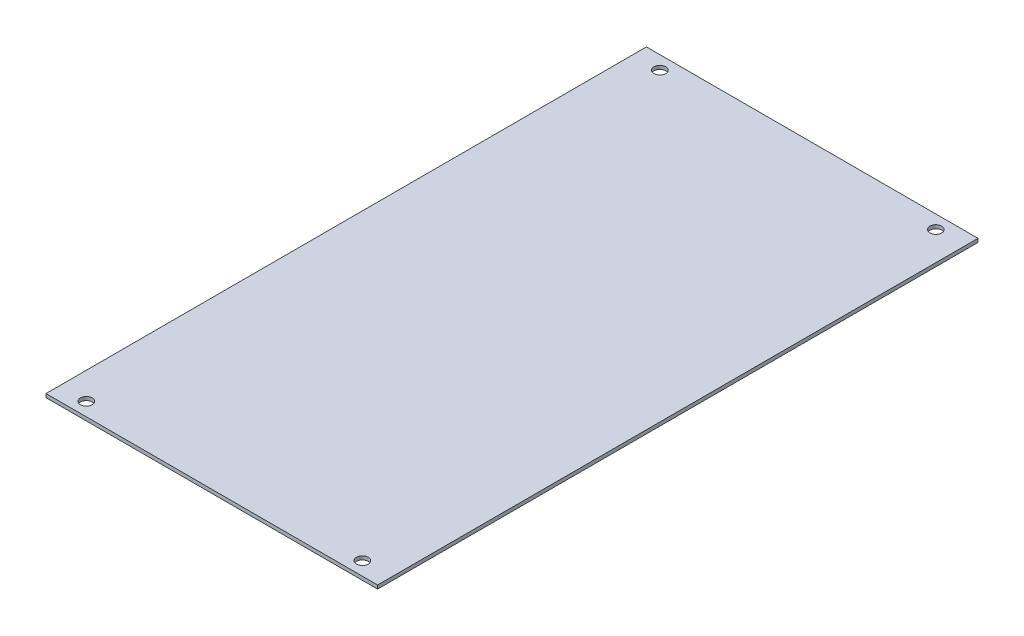
SolidWorks part; units mm, degrees
material "1.4301 (X5CrNi18-10)"
ref_plane "Vorne" through (0, 0, 0) normal (0, 0, 1) x (1, 0, 0)
ref_plane "Oben" through (0, 0, 0) normal (0, 1, 0) x (1, 0, 0)
ref_plane "Rechts" through (0, 0, 0) normal (1, 0, 0) x (0, 0, -1)
sketch "Skizze2" plane through (0, 0, 0) normal (0, 1, 0) x (1, 0, 0)
  line L1 (-92.5, 167.5) -> (92.5, 167.5)
  line L2 (-92.5, 167.5) -> (-92.5, -167.5)
  line L3 (-92.5, -167.5) -> (92.5, -167.5)
  line L4 (92.5, 167.5) -> (92.5, -167.5)
  line L5 (-92.5, 167.5) -> (92.5, -167.5) construction
  line L6 (-92.5, -167.5) -> (92.5, 167.5) construction
  point P0 (0, 0)
  dimension "D1" = 185
  dimension "D2" = 335
sheet metal parameters "Blech1" thickness 2 parameters "D1"=0.1, "Dicke"=2
base flange "Basis-Blech1" sketch "Skizze2" thickness 2 reverse thickness direction no parameters "D1"=0.1
hole_wizard "Durchgangsloch für M61" positions "Skizze27" profile "Skizze26" hole size "M6" standard "Gabler-Normteile" end condition through all
sketch "Skizze27" plane through (0, -2, 0) normal (0, -1, 0) x (-1, 0, 0)
  line L0 (0, 0) -> (0, 167.5) construction
  line L5 (-92.5, 167.5) -> (92.5, 167.5) construction
  line L6 (0, 0) -> (-92.5, 0) construction
  line L8 (-92.5, -167.5) -> (-92.5, 167.5) construction
  line L9 (92.5, 167.5) -> (92.5, -167.5) construction
  point P0 (-76.5, -160)
  point P2 (77.5, -160)
  point P15 (77.5, 160)
  point P17 (-76.5, 160)
  point P42 (0, 0)
  point P45 (0, 0)
  point P46 (0, 0)
  point P48 (0, 0)
  point P49 (0, 0)
  point P50 (0, 0)
  point P51 (0, 0)
  dimension "D1" = 154
  dimension "D2" = 15
  dimension "D3" = 7.5
sketch "Skizze26" plane through (76.5, -2, 160) normal (1, 0, 0) x (0, 0, -1)
  line L0 (0, 0) -> (0, 2)
  line L1 (0, 2) -> (3.3, 2)
  line L2 (3.3, 2) -> (3.3, 0)
  line L5 (3.3, 0) -> (0, 0)
  line L11 (0, -6.35) -> (0, 107.95) construction
  dimension "Bohrerdurchmesser" = 6.6
  dimension "Bohrungstiefe" = 2
flat pattern "Abwicklung1" [suppressed]
sketch "Biegung-Linien1" plane through (0, -2, 0) normal (0, -1, 0) x (1, 0, 0)
sketch3d "Rahmen1" [suppressed]
  line L0 (-350, -335, 0) -> (-350, 0, 0) construction
  line L1 (-165, -335, 0) -> (-165, 0, 0) construction
  line L2 (-350, -335, 0) -> (-165, -335, 0) construction
  line L3 (-350, 0, 0) -> (-165, 0, 0) construction
